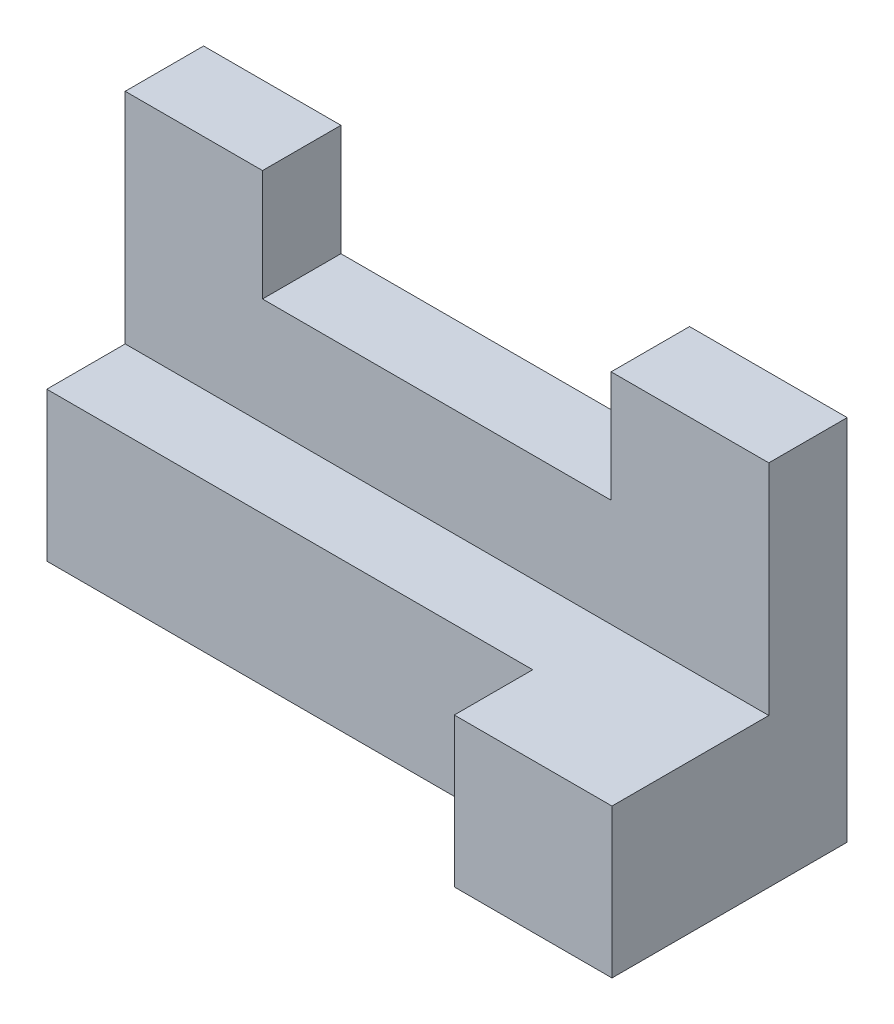
SolidWorks part; units mm, degrees
ref_plane "前基準面" through (0, 0, 0) normal (0, 0, 1) x (1, 0, 0)
ref_plane "上基準面" through (0, 0, 0) normal (0, 1, 0) x (1, 0, 0)
ref_plane "右基準面" through (0, 0, 0) normal (1, 0, 0) x (0, 0, -1)
sketch "草圖1" plane through (0, 0, 0) normal (0, 0, 1) x (1, 0, 0)
  line L0 (-39.5063, 0) -> (42.5747, 0)
  line L1 (-39.5063, 0) -> (-39.5063, 27.9037)
  line L2 (42.5747, 0) -> (42.5747, 27.9037)
  line L3 (42.5747, 27.9037) -> (22.4652, 27.9037)
  line L4 (22.4652, 27.9037) -> (22.4652, 13.7199)
  line L5 (22.4652, 13.7199) -> (-21.9936, 13.7199)
  line L6 (-21.9936, 13.7199) -> (-21.9936, 27.9037)
  line L7 (-21.9936, 27.9037) -> (-39.5063, 27.9037)
  line L8 (-39.5063, 0) -> (-39.5063, -18.9922)
  line L9 (-39.5063, -18.9922) -> (42.5747, -18.9922)
  line L10 (42.5747, -18.9922) -> (42.5747, 0)
  line L11 (42.5747, 0) -> (43.1333, 0.4863)
  line L12 (22.4652, 0) -> (22.4652, -18.9922)
extrude "填料-伸長1" add sketch "草圖1" along normal blind 10 contours L6 L7 L1 L0 L2 L3 L4 L5 region at (2.0275, 11.3456, 0)
extrude "填料-伸長2" add sketch "草圖1<3>" along normal blind 30 contours L0 L12 L9 L10 region at (32.52, -9.4961, 0)
sketch "草圖1<3>" plane through (0, 0, 0) normal (0, 0, 1) x (1, 0, 0) same geometry as "草圖1"
extrude "填料-伸長3" add sketch "草圖1<4>" along normal blind 20 contours L12 L0 L8 L9 region at (-8.5206, -9.4961, 0)
sketch "草圖1<4>" plane through (0, 0, 0) normal (0, 0, 1) x (1, 0, 0) same geometry as "草圖1"
